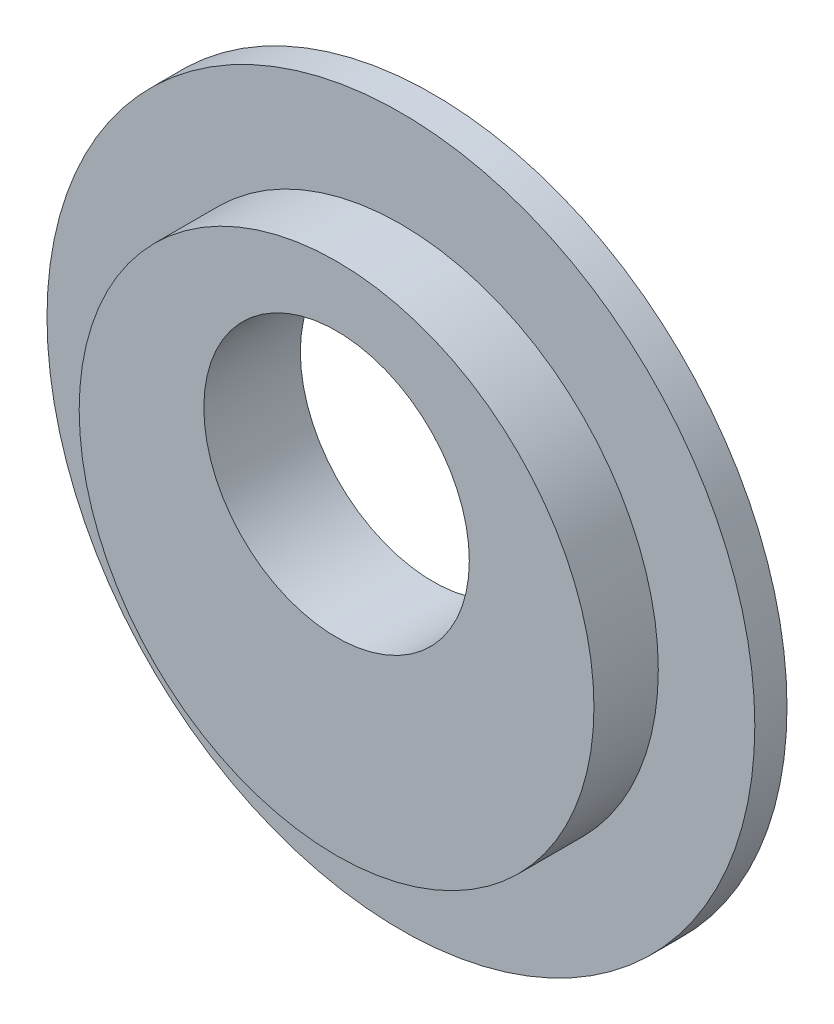
SolidWorks part; units mm, degrees
material "Custom Plastic"
ref_plane "X-Y Datum" through (0, 0, 0) normal (0, 0, 1) x (1, 0, 0)
ref_plane "X-Z Datum" through (0, 0, 0) normal (0, 1, 0) x (1, 0, 0)
ref_plane "Y-Z Datum" through (0, 0, 0) normal (1, 0, 0) x (0, 0, -1)
sketch "Sketch1" plane through (0, 0, 0) normal (0, 0, 1) x (1, 0, 0)
  circle A0 centre (0, 0) radius 12.7
  circle A1 centre (0, 0) radius 17.4625
  circle A3 centre (0, 3.175) radius 6.55
  dimension "D1" = 25.4
  dimension "D3" = 13.1
  dimension "D4" = 3.175
  dimension "D2" = 4.7625
extrude "Boss-Extrude1" add sketch "Sketch1" along normal blind 1.5875 contours A0 A3 | A1 A0 region at (-12.3408, 0, 0) region at (-16.9686, 0, 0)
sketch "Sketch4" plane through (0, 0, 1.5875) normal (0, 0, 1) x (1, 0, 0)
  circle A1 centre (0, 3.175) radius 6.55
  circle A2 centre (0, 3.175) radius 6.55
  circle A3 centre (0, 0) radius 17.4625
  circle A4 centre (0, 0) radius 17.4625
  circle A5 centre (0, 0) radius 12.7
  circle A6 centre (0, 0) radius 12.7
  circle M4 centre (0, 3.175) radius 6.55
  dimension "D1" = 0
  dimension "D2" = 0
  dimension "D3" = 0
extrude "Boss-Extrude3" add sketch "Sketch4" along normal blind 3.175 contours A6 M4 region at (-12.3408, 0, 1.5875)
